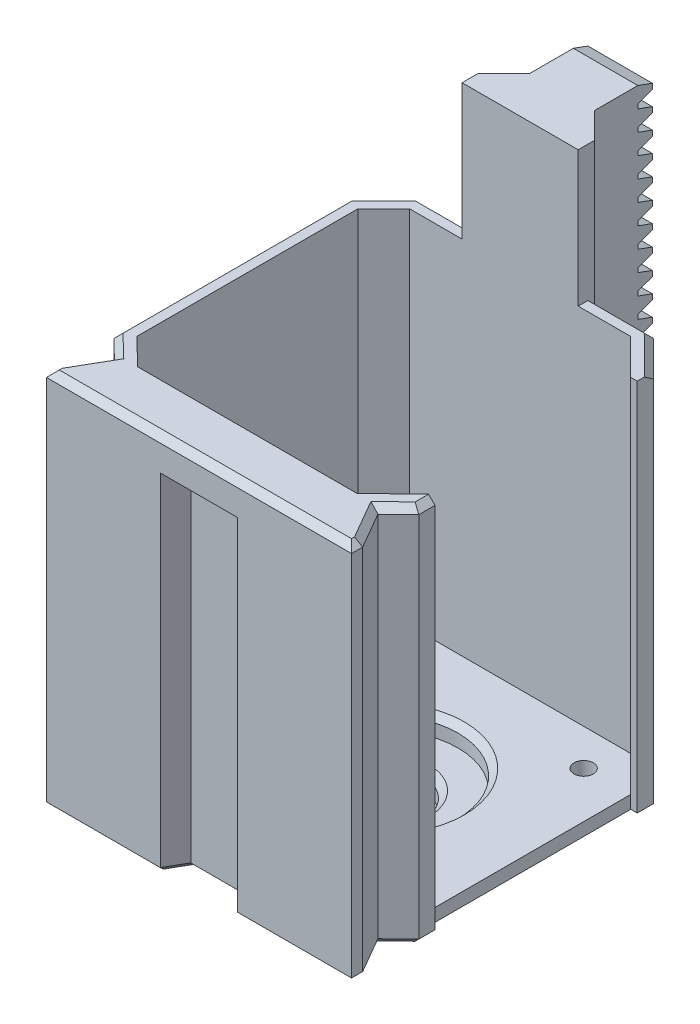
SolidWorks part; units mm, degrees
ref_plane "Front Plane" through (0, 0, 0) normal (0, 0, 1) x (1, 0, 0)
ref_plane "Top Plane" through (0, 0, 0) normal (0, 1, 0) x (1, 0, 0)
ref_plane "Right Plane" through (0, 0, 0) normal (1, 0, 0) x (0, 0, -1)
sketch "Sketch1" plane through (0, 0, 0) normal (0, 1, 0) x (1, 0, 0)
  line L0 (-21.15, 17.15) -> (-17.15, 21.15)
  line L1 (-17, -21.15) -> (17, -21.15)
  line L2 (-21.15, -17.15) -> (-21.15, 17.15)
  line L3 (-17.15, 21.15) -> (17.15, 21.15)
  line L4 (21.15, -17.15) -> (21.15, 17.15)
  line L5 (-21.15, -21.15) -> (21.15, 21.15) construction
  line L6 (-21.15, 21.15) -> (21.15, -21.15) construction
  line L7 (-21.15, -17.15) -> (-17, -21.15)
  line L8 (17, -21.15) -> (21.15, -17.15)
  line L9 (17.15, 21.15) -> (21.15, 17.15)
  circle A0 centre (-15.5, 15.5) radius 1.5
  circle A1 centre (15.5, 15.5) radius 1.5
  circle A2 centre (15.5, -15.5) radius 1.5
  circle A3 centre (-15.5, -15.5) radius 1.5
  circle A4 centre (0, 0) radius 11.5
  point P0 (0, 0)
  dimension "D3" = 3
  dimension "D4" = 3
  dimension "D9" = 3
  dimension "D10" = 3
  dimension "D12" = 23
  dimension "D1" = 42.3
  dimension "D2" = 42.3
  dimension "D11" = 31
  dimension "D13" = 34
  dimension "D6" = 4
  dimension "D7" = 4
extrude "Mount Face Extrude" add sketch "Sketch1" along normal blind 3
chamfer "Bracket Mount Hole Chamfer" distance 0.75 angle 45 4 edges at (-15.5, 0, -14) (15.5, 0, -14) (15.5, 0, 17) (-15.5, 0, 17)
sketch "Sketch5" plane through (0, 0, 0) normal (0, 1, 0) x (1, 0, 0)
  line L0 (21.15, -17.15) -> (22.65, -15.7042)
  line L1 (23.65, -14.7404) -> (23.65, 14.65) construction
  line L3 (-24.65, -28.65) -> (24.65, -28.65) construction
  line L5 (-23.65, -26.9179) -> (-23.65, -28.65)
  line L6 (-23.65, -28.65) -> (23.65, -28.65)
  line L7 (23.65, -28.65) -> (23.65, -26.9179)
  line L8 (-23.65, -26.9179) -> (-24.65, -28.65) construction
  line L9 (24.65, -28.65) -> (23.65, -26.9179) construction
  line L10 (22.65, 15.65) -> (23.65, 15.65)
  line L11 (22.65, -15.7042) -> (23.65, -15.7042)
  line L12 (23.65, 14.65) -> (23.65, 15.65) construction
  line L13 (22.65, 15.65) -> (23.65, 14.65) construction
  line L14 (23.65, -15.7042) -> (23.65, -14.7404) construction
  line L15 (22.65, -15.7042) -> (23.65, -14.7404) construction
  line L16 (-23.65, 18.1855) -> (-23.65, -18.2126)
  line L17 (-23.65, -18.2126) -> (-18.0087, -23.65)
  line L18 (-18.0087, -23.65) -> (18.0087, -23.65)
  line L19 (18.0087, -23.65) -> (23.65, -18.2126)
  line L20 (23.65, -18.2126) -> (23.65, 18.1855)
  line L21 (23.65, 18.1855) -> (18.1855, 23.65)
  line L22 (18.1855, 23.65) -> (-18.1855, 23.65)
  line L23 (-18.1855, 23.65) -> (-23.65, 18.1855)
  line L24 (-23.65, 14.65) -> (-23.65, -18.2126)
  line L25 (-23.65, -18.2126) -> (-20.4209, -21.325)
  line L26 (-18.0087, -23.65) -> (18.0087, -23.65) construction
  line L27 (20.4209, -21.325) -> (23.65, -18.2126)
  line L28 (23.65, -18.2126) -> (23.65, -15.7042)
  line L29 (23.65, 18.1855) -> (18.1855, 23.65)
  line L30 (18.1855, 23.65) -> (-18.1855, 23.65)
  line L31 (-18.1855, 23.65) -> (-23.65, 18.1855)
  line L32 (-21.15, 17.15) -> (-23.65, 14.65) construction
  line L33 (21.15, 17.15) -> (22.65, 15.65)
  line L34 (-23.65, 18.1855) -> (-23.65, 14.65)
  line L35 (23.65, 15.65) -> (23.65, 18.1855)
  line L36 (-23.65, -26.9179) -> (-20.4209, -21.325)
  line L38 (20.4209, -21.325) -> (23.65, -26.9179)
  line L40 (-21.15, 17.15) -> (-21.15, -17.15)
  line L41 (-21.15, -17.15) -> (-17, -21.15)
  line L42 (-17, -21.15) -> (17, -21.15)
  line L43 (17, -21.15) -> (21.15, -17.15)
  line L44 (21.15, -17.15) -> (21.15, 17.15)
  line L45 (21.15, 17.15) -> (17.15, 21.15)
  line L46 (17.15, 21.15) -> (-17.15, 21.15)
  line L47 (-17.15, 21.15) -> (-21.15, 17.15)
  line L48 (-21.15, 17.15) -> (-21.15, -17.15)
  line L49 (-21.15, -17.15) -> (-17, -21.15)
  line L50 (-17, -21.15) -> (17, -21.15)
  line L51 (17, -21.15) -> (21.15, -17.15)
  line L52 (21.15, -17.15) -> (21.15, 17.15) construction
  line L53 (21.15, 17.15) -> (17.15, 21.15)
  line L54 (17.15, 21.15) -> (-17.15, 21.15)
  line L55 (-17.15, 21.15) -> (-21.15, 17.15)
  line L60 (-20.4209, -21.325) -> (-18.0087, -23.65) construction
  line L61 (18.0087, -23.65) -> (20.4209, -21.325) construction
  point P32 (0, -28.65)
  dimension "D3" = 47.3
  dimension "D4" = 60
  dimension "D5" = 47.3
  dimension "D6" = 1
  dimension "D7" = 5
  dimension "D8" = 1
  dimension "D1" = 2.5
  dimension "D2" = 0
extrude "Main Body Extrude" add sketch "Sketch5" along normal blind 59
sketch "Sketch37" plane through (0, 0, 0) normal (0, -1, 0) x (1, 0, 0)
  line L0 (21.15, -17.15) -> (22.65, -15.65) construction
  line L1 (21.15, 17.15) -> (21.15, -17.15) construction
  line L2 (22.65, 15.7042) -> (21.15, 17.15) construction
  line L3 (21.15, -17.15) -> (22.65, -15.65)
  line L4 (21.15, 17.15) -> (21.15, -17.15)
  line L5 (22.65, 15.7042) -> (21.15, 17.15)
  line L6 (22.65, 15.7042) -> (22.65, -15.65)
extrude "Front Face Fill in Extrude" add sketch "Sketch37" against normal up to surface (3 mm away) up to face at (0, 3, 0)
sketch "Sketch39" plane through (0, 0, 0) normal (0, -1, 0) x (1, 0, 0)
  line L0 (-6, 28.65) -> (-4.2679, 25.65)
  line L1 (-23.65, 28.65) -> (23.65, 28.65) construction
  line L2 (-4.2679, 25.65) -> (4.2679, 25.65)
  line L3 (4.2679, 25.65) -> (6, 28.65)
  line L4 (6, 28.65) -> (-6, 28.65)
  line L5 (0, 0) -> (0, 25.65) construction
  dimension "D1" = 3
  dimension "D2" = 12
  dimension "D3" = 60
extrude "Limit Tab" cut sketch "Sketch39" against normal offset from surface (54 mm away) 5 up to face at (2.2864, 59, 4.8477)
sketch "Sketch13" plane through (0, 0, 0) normal (1, 0, 0) x (0, 0, -1)
  line L0 (36.65, 6.9244) -> (36.65, 6.0816)
  line L1 (36.65, 6.0816) -> (34.4, 5.2626)
  line L2 (34.4, 5.2626) -> (34.4, 4.6018)
  line L3 (34.4, 4.6018) -> (36.65, 3.7828)
  line L4 (36.65, 10.066) -> (36.65, 9.2232)
  line L5 (36.65, 9.2232) -> (34.4, 8.4042)
  line L6 (34.4, 8.4042) -> (34.4, 7.7434)
  line L7 (34.4, 7.7434) -> (36.65, 6.9244)
  line L8 (36.65, 13.2076) -> (36.65, 12.3648)
  line L9 (36.65, 12.3648) -> (34.4, 11.5458)
  line L10 (34.4, 11.5458) -> (34.4, 10.885)
  line L11 (34.4, 10.885) -> (36.65, 10.066)
  line L12 (36.65, 16.3492) -> (36.65, 15.5064)
  line L13 (36.65, 15.5064) -> (34.4, 14.6874)
  line L14 (34.4, 14.6874) -> (34.4, 14.0266)
  line L15 (34.4, 14.0266) -> (36.65, 13.2076)
  line L16 (36.65, 19.4908) -> (36.65, 18.648)
  line L17 (36.65, 18.648) -> (34.4, 17.829)
  line L18 (34.4, 17.829) -> (34.4, 17.1681)
  line L19 (34.4, 17.1681) -> (36.65, 16.3492)
  line L20 (36.65, 22.6324) -> (36.65, 21.7895)
  line L21 (36.65, 21.7895) -> (34.4, 20.9706)
  line L22 (34.4, 20.9706) -> (34.4, 20.3097)
  line L23 (34.4, 20.3097) -> (36.65, 19.4908)
  line L24 (36.65, 25.774) -> (36.65, 24.9311)
  line L25 (36.65, 24.9311) -> (34.4, 24.1122)
  line L26 (34.4, 24.1122) -> (34.4, 23.4513)
  line L27 (34.4, 23.4513) -> (36.65, 22.6324)
  line L28 (36.65, 28.9156) -> (36.65, 28.0727)
  line L29 (36.65, 28.0727) -> (34.4, 27.2538)
  line L30 (34.4, 27.2538) -> (34.4, 26.5929)
  line L31 (34.4, 26.5929) -> (36.65, 25.774)
  line L32 (36.65, 32.0572) -> (36.65, 31.2143)
  line L33 (36.65, 31.2143) -> (34.4, 30.3954)
  line L34 (34.4, 30.3954) -> (34.4, 29.7345)
  line L35 (34.4, 29.7345) -> (36.65, 28.9156)
  line L36 (36.65, 35.1988) -> (36.65, 34.3559)
  line L37 (36.65, 34.3559) -> (34.4, 33.537)
  line L38 (34.4, 33.537) -> (34.4, 32.8761)
  line L39 (34.4, 32.8761) -> (36.65, 32.0572)
  line L40 (36.65, 38.3404) -> (36.65, 37.4975)
  line L41 (36.65, 37.4975) -> (34.4, 36.6786)
  line L42 (34.4, 36.6786) -> (34.4, 36.0177)
  line L43 (34.4, 36.0177) -> (36.65, 35.1988)
  line L44 (36.65, 41.482) -> (36.65, 40.6391)
  line L45 (36.65, 40.6391) -> (34.4, 39.8202)
  line L46 (34.4, 39.8202) -> (34.4, 39.1593)
  line L47 (34.4, 39.1593) -> (36.65, 38.3404)
  line L48 (36.65, 44.6235) -> (36.65, 43.7807)
  line L49 (36.65, 43.7807) -> (34.4, 42.9618)
  line L50 (34.4, 42.9618) -> (34.4, 42.3009)
  line L51 (34.4, 42.3009) -> (36.65, 41.482)
  line L52 (36.65, 47.7651) -> (36.65, 46.9223)
  line L53 (36.65, 46.9223) -> (34.4, 46.1034)
  line L54 (34.4, 46.1034) -> (34.4, 45.4425)
  line L55 (34.4, 45.4425) -> (36.65, 44.6235)
  line L56 (36.65, 50.9067) -> (36.65, 50.0639)
  line L57 (36.65, 50.0639) -> (34.4, 49.2449)
  line L58 (34.4, 49.2449) -> (34.4, 48.5841)
  line L59 (34.4, 48.5841) -> (36.65, 47.7651)
  line L60 (36.65, 54.0483) -> (36.65, 53.2055)
  line L61 (36.65, 53.2055) -> (34.4, 52.3865)
  line L62 (34.4, 52.3865) -> (34.4, 51.7257)
  line L63 (34.4, 51.7257) -> (36.65, 50.9067)
  line L64 (36.65, 57.1899) -> (36.65, 56.3471)
  line L65 (36.65, 56.3471) -> (34.4, 55.5281)
  line L66 (34.4, 55.5281) -> (34.4, 54.8673)
  line L67 (34.4, 54.8673) -> (36.65, 54.0483)
  line L68 (36.65, 60.3315) -> (36.65, 59.4887)
  line L69 (36.65, 59.4887) -> (34.4, 58.6697)
  line L70 (34.4, 58.6697) -> (34.4, 58.0089)
  line L71 (34.4, 58.0089) -> (36.65, 57.1899)
  line L72 (36.65, 63.4731) -> (36.65, 62.6302)
  line L73 (36.65, 62.6302) -> (34.4, 61.8113)
  line L74 (34.4, 61.8113) -> (34.4, 61.1504)
  line L75 (34.4, 61.1504) -> (36.65, 60.3315)
  line L76 (36.65, 66.6147) -> (36.65, 65.7718)
  line L77 (36.65, 65.7718) -> (34.4, 64.9529)
  line L78 (34.4, 64.9529) -> (34.4, 64.292)
  line L79 (34.4, 64.292) -> (36.65, 63.4731)
  line L80 (36.65, 69.7563) -> (36.65, 68.9134)
  line L81 (36.65, 68.9134) -> (34.4, 68.0945)
  line L82 (34.4, 68.0945) -> (34.4, 67.4336)
  line L83 (34.4, 67.4336) -> (36.65, 66.6147)
  line L84 (36.65, 72.8979) -> (36.65, 72.055)
  line L85 (36.65, 72.055) -> (34.4, 71.2361)
  line L86 (34.4, 71.2361) -> (34.4, 70.5752)
  line L87 (34.4, 70.5752) -> (36.65, 69.7563)
  line L88 (36.65, 76.0395) -> (36.65, 75.1966)
  line L89 (36.65, 75.1966) -> (34.4, 74.3777)
  line L90 (34.4, 74.3777) -> (34.4, 73.7168)
  line L91 (34.4, 73.7168) -> (36.65, 72.8979)
  line L92 (36.65, 79.1811) -> (36.65, 78.3382)
  line L93 (36.65, 78.3382) -> (34.4, 77.5193)
  line L94 (34.4, 77.5193) -> (34.4, 76.8584)
  line L95 (34.4, 76.8584) -> (36.65, 76.0395)
  line L98 (36.65, 3.7828) -> (36.65, 2.94)
  line L99 (36.65, 2.94) -> (34.4, 2.1211)
  line L100 (34.4, 2.1211) -> (34.4, 1.4602)
  line L101 (34.4, 1.4602) -> (36.65, 0.6413)
  line L102 (36.65, 0.6413) -> (36.65, 0)
  line L103 (36.65, 0) -> (23.65, 0)
  line L104 (23.65, 0) -> (23.65, 80)
  line L105 (23.65, 59) -> (23.65, 0) construction
  line L106 (23.65, 80) -> (34.4, 80)
  line L108 (34.4, 80) -> (36.65, 79.1811)
  line L147 (18.1855, 0) -> (23.65, 0) construction
  line L148 (34.4, 80.6609) -> (34.4, 80) [skipped]
  line L149 (36.65, 81.4798) -> (34.4, 80.6609) [skipped]
  line L150 (36.65, 82.3227) -> (36.65, 81.4798) [skipped]
  line L151 (34.4, 83.1416) -> (36.65, 82.3227) [skipped]
  line L152 (36.65, 84.6214) -> (34.4, 83.8025) [skipped]
  line L153 (34.4, 86.2832) -> (36.65, 85.4643) [skipped]
  line L154 (36.65, 87.763) -> (34.4, 86.9441) [skipped]
  line L155 (34.4, 89.4248) -> (36.65, 88.6058) [skipped]
  line L156 (36.65, 90.9046) -> (34.4, 90.0856) [skipped]
  line L157 (34.4, 92.5664) -> (36.65, 91.7474) [skipped]
  line L158 (34.4, 83.8025) -> (34.4, 83.1416) [skipped]
  line L159 (34.4, 86.9441) -> (34.4, 86.2832) [skipped]
  line L160 (36.65, 85.4643) -> (36.65, 84.6214) [skipped]
  line L161 (36.65, 88.6058) -> (36.65, 87.763) [skipped]
  line L162 (34.4, 90.0856) -> (34.4, 89.4248) [skipped]
  line L163 (36.65, 91.7474) -> (36.65, 90.9046) [skipped]
  line L164 (34.4, 93.2272) -> (34.4, 92.5664) [skipped]
  line L165 (36.65, 94.0462) -> (34.4, 93.2272) [skipped]
  line L166 (36.65, 94.889) -> (36.65, 94.0462) [skipped]
  line L167 (34.4, 95.708) -> (36.65, 94.889) [skipped]
  line L168 (34.4, 96.3688) -> (34.4, 95.708) [skipped]
  line L169 (36.65, 97.1878) -> (34.4, 96.3688) [skipped]
  line L170 (36.65, 98.0306) -> (36.65, 97.1878) [skipped]
  line L171 (34.4, 98.8496) -> (36.65, 98.0306) [skipped]
  line L172 (34.4, 99.5104) -> (34.4, 98.8496) [skipped]
  line L173 (36.65, 100.3294) -> (34.4, 99.5104) [skipped]
  line L174 (36.65, 101.1722) -> (36.65, 100.3294) [skipped]
  line L175 (34.4, 101.9911) -> (36.65, 101.1722) [skipped]
  line L176 (34.4, 102.652) -> (34.4, 101.9911) [skipped]
  line L177 (36.65, 110.597) -> (36.65, 109.7541) [skipped]
  line L178 (36.65, 109.7541) -> (34.4, 108.9352) [skipped]
  line L179 (34.4, 108.9352) -> (34.4, 108.2743) [skipped]
  line L180 (34.4, 108.2743) -> (36.65, 107.4554) [skipped]
  line L181 (36.65, 107.4554) -> (36.65, 106.6125) [skipped]
  line L182 (36.65, 106.6125) -> (34.4, 105.7936) [skipped]
  line L183 (34.4, 105.7936) -> (34.4, 105.1327) [skipped]
  line L184 (34.4, 105.1327) -> (36.65, 104.3138) [skipped]
  line L185 (36.65, 104.3138) -> (36.65, 103.471) [skipped]
  line L186 (36.65, 103.471) -> (34.4, 102.652) [skipped]
  point P14 (23.65, 80)
  dimension "D1" = 80
  dimension "D2" = 0.8429
  dimension "D3" = 0.6609
  dimension "D4" = 2.2987
  dimension "D5" = 13
  dimension "D6" = 0.6413
  dimension "D7" = 20
  dimension "D8" = 3.1416
  dimension "D9" = 35
extrude "Rack Extrude" add sketch "Sketch13" against normal mid plane 10
sketch "Rack Line" plane through (0, 0, 0) normal (1, 0, 0) x (0, 0, -1)
  line L0 (35.65, 0) -> (35.65, 80)
  line L1 (23.65, 0) -> (36.65, 0) construction
  line L3 (23.65, 59) -> (23.65, 0) construction
  point P4 (35.65, 80)
  dimension "D1" = 12
chamfer "Rack Chamfer" distance 4 angle 45 2 edges at (5, 29.5, -23.65) (-5, 29.5, -23.65)
sketch "Sketch15" plane through (0, 59, 0) normal (0, 1, 0) x (1, 0, 0)
  line L0 (-5, 27.65) -> (-9, 23.65)
  line L1 (17.15, 21.15) -> (-17.15, 21.15) construction
  line L2 (-9, 21.15) -> (9, 21.15)
  line L3 (9, 23.65) -> (5, 27.65)
  line L4 (5, 27.65) -> (-5, 27.65)
  line L5 (9, 23.65) -> (5, 27.65) construction
  line L6 (-5, 27.65) -> (-9, 23.65) construction
  line L9 (-9, 23.65) -> (-9, 21.15)
  line L10 (9, 23.65) -> (9, 21.15)
  line L11 (-11.5, 21.15) -> (-9, 21.15) construction
  line L12 (-9, 23.65) -> (-11.5, 21.15) construction
  line L13 (9, 21.15) -> (11.5, 21.15) construction
  line L14 (11.5, 21.15) -> (9, 23.65) construction
  line L15 (-9, 23.65) -> (-18.1855, 23.65) construction
  line L16 (-5, 27.65) -> (-5, 36.65) construction
extrude "Rack Support Base Extrude" add sketch "Sketch15" along normal up to surface (21 mm away) up to face at (0, 80, -29.025)
sketch "Sketch27" plane through (0, 0, 0) normal (0, -1, 0) x (-1, 0, 0)
  circle A4 centre (0, 0) radius 13.6
  circle A5 centre (0, 0) radius 11.5 construction
  circle A6 centre (0, 0) radius 11.5
  circle A7 centre (0, 0) radius 6
  circle M47 centre (0, 0) radius 11.5
  dimension "D1" = 12
  dimension "D4" = 27.2
extrude "Face Cosmetic Ring Extrude" add sketch "Sketch27" along normal blind 4 contours A4 M47 | A7 M47 region at (13.2153, 0, 0) region at (11.1747, 0, 0)
chamfer "Face Cosmetic Ring Main Chamfer" distance 4 angle 45 1 edges at (0, 0, -13.6)
chamfer "Face Cosmetic Ring Main Through Hole Chamfer" distance 1 angle 45 3 edges at (0, -4, -6) (0, 0, -6) (0, 3, 11.5)
chamfer "Front/Back Face Chamfer" distance 1 angle 45 36 edges at (13.5928, 59, -23.65) (20.9178, 59, -20.9178) (23.65, 59, 16.9584) (22.0354, 59, 19.7688) (0, 59, 28.65) (-22.0354, 59, 19.7688) (-23.65, 59, 0.0135) (-20.9178, 59, -20.9178) (-13.5928, 59, -23.65) (-7, 0, -25.65) (-13.5928, 0, -23.65) (-20.9178, 0, -20.9178) (7, 0, -25.65) (13.5928, 0, -23.65) (20.9178, 0, -20.9178) (23.65, 0, -16.9178) (23.15, 0, -15.65) (22.65, 0, 0.0271) (23.15, 0, 15.7042) (23.65, 0, 16.9584) (22.0354, 0, 19.7688) (14.825, 0, 28.65) (5.134, 0, 27.15) (0, 0, 25.65) (-5.134, 0, 27.15) (-14.825, 0, 28.65) (-22.0354, 0, 19.7688) (-23.65, 0, 0.0135) (23.65, 59, 27.784) (-23.65, 59, 27.784) (23.65, 0, 27.784) (-23.65, 0, 27.784) (22.0354, 0, 24.1215) (-22.0354, 0, 24.1215) (22.0354, 59, 24.1215) (-22.0354, 59, 24.1215)
